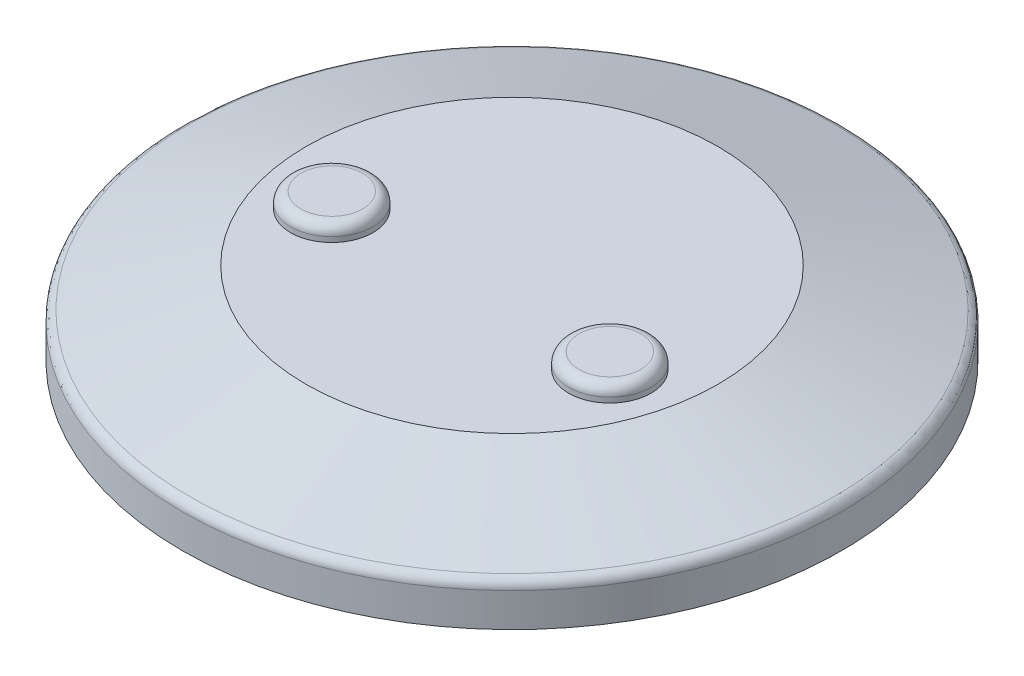
SolidWorks part; units mm, degrees
material "1060 Alloy"
ref_plane "Front Plane" through (0, 0, 0) normal (0, 0, 1) x (1, 0, 0)
ref_plane "Top Plane" through (0, 0, 0) normal (0, 1, 0) x (1, 0, 0)
ref_plane "Right Plane" through (0, 0, 0) normal (1, 0, 0) x (0, 0, -1)
sketch "Sketch1" plane through (0, 0, 0) normal (0, 1, 0) x (1, 0, 0)
  circle A0 centre (0, 0) radius 32
  dimension "D1" = 64
extrude "Boss-Extrude1" add sketch "Sketch1" along normal blind 4
sketch "Sketch2" plane through (0, 4, 0) normal (0, 1, 0) x (1, 0, 0)
  circle A0 centre (0, 0) radius 32 construction
  circle A1 centre (0, 0) radius 32
ref_plane "Plane1" through (0, 8, 0) normal (0, 1, 0) x (-1, 0, 0)
sketch "Sketch3" plane through (0, 8, 0) normal (0, 1, 0) x (-1, 0, 0)
  circle A0 centre (0, 0) radius 20
  dimension "D1" = 40
loft "Loft1" add profiles "Sketch3", "Sketch2" connector at (5.3272, 8, -19.2775) connector at (9.6903, 4, -30.4975)
fillet "Fillet1" radius 1 1 edges at (0, 4, 32)
sketch "Sketch4" plane through (0, 8, 0) normal (0, 1, 0) x (1, 0, 0)
  line L0 (0, 20) -> (0, -20) construction
  line L1 (-13.5, -4) -> (0, -4) construction
  line L2 (0, -4) -> (13.5, -4) construction
  circle A0 centre (0, 0) radius 20 construction
  circle A1 centre (-13.5, -4) radius 4
  circle A2 centre (13.5, -4) radius 4
  circle A3 centre (0, 0) radius 32 construction
  dimension "D1" = 8
  dimension "D2" = 27
  dimension "D3" = 4
extrude "Boss-Extrude2" add sketch "Sketch4" along normal blind 1.5
fillet "Fillet2" radius 1 2 edges at (-13.5, 9.5, 8) (13.5, 9.5, 8)
ref_plane "Plane2" through (0, 0, 4) normal (0, 0, 1) x (1, 0, 0)
ref_axis "Axis2" through (0, 9.975, 4) along (0, -1, 0)
